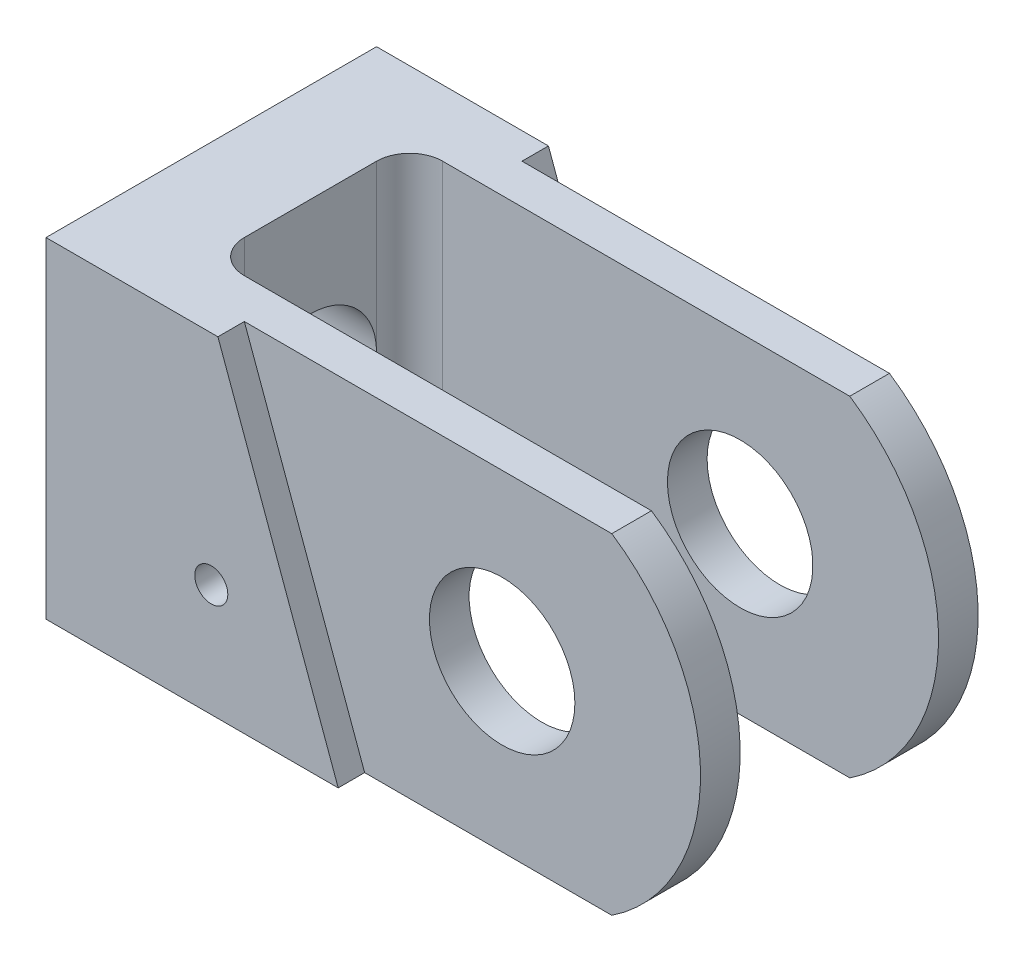
SolidWorks part; units mm, degrees
ref_plane "Front Plane" through (0, 0, 0) normal (0, 0, 1) x (1, 0, 0)
ref_plane "Top Plane" through (0, 0, 0) normal (0, 1, 0) x (1, 0, 0)
ref_plane "Right Plane" through (0, 0, 0) normal (1, 0, 0) x (0, 0, -1)
sketch "Sketch1" plane through (0, 0, 0) normal (0, 0, 1) x (1, 0, 0)
  line L1 (35.4458, -24.1953) -> (-46.1373, -24.1953)
  line L3 (35.4458, 25.8047) -> (-46.1373, 25.8047)
  line L4 (-46.1373, -24.1953) -> (-46.1373, 25.8047)
  line L5 (38.9579, -21.4704) -> (-46.1373, 25.8047) construction
  line L6 (38.9579, 23.0799) -> (-46.1373, -24.1953) construction
  circle A0 centre (18.8627, 0.8047) radius 11
  arc A2 (35.4458, -24.1953) -> (35.4458, 25.8047) centre (18.8627, 0.8047) ccw
  point P0 (-1.1373, 0.8047)
  dimension "D3" = 22
  dimension "D1" = 50
  dimension "D4" = 65
extrude "Boss-Extrude1" add sketch "Sketch1" along normal blind 50
sketch "Sketch2" plane through (-46.1373, 0, 0) normal (-1, 0, 0) x (0, 0, 1)
  line L0 (50, 25.8047) -> (0, 25.8047) construction
  line L1 (50, 25.8047) -> (50, -24.1953) construction
  circle A0 centre (25, 0.8047) radius 17.5
  dimension "D1" = 35
  dimension "D2" = 25
  dimension "D3" = 25
extrude "Cut-Extrude1" cut sketch "Sketch2" against normal blind 2
sketch "Sketch3" plane through (-44.1373, 0, 0) normal (-1, 0, 0) x (0, 0, 1)
  line L0 (50, 25.8047) -> (0, 25.8047) construction
  line L1 (50, 25.8047) -> (50, -24.1953) construction
  circle A0 centre (25, 0.8047) radius 10
  dimension "D1" = 20
  dimension "D2" = 25
  dimension "D3" = 25
extrude "Cut-Extrude2" cut sketch "Sketch3" against normal through all
sketch "Sketch4" plane through (0, 0, 50) normal (0, 0, 1) x (1, 0, 0)
  line L0 (-20.1373, 25.8047) -> (-1.9388, -24.1953)
  line L1 (35.4458, 25.8047) -> (-46.1373, 25.8047) construction
  line L2 (-46.1373, -24.1953) -> (35.4458, -24.1953) construction
  line M3 (-46.1373, -24.1953) -> (35.4458, -24.1953)
  arc M4 (35.4458, -24.1953) -> (35.4458, 25.8047) centre (18.8627, 0.8047) ccw
  line M5 (35.4458, 25.8047) -> (-46.1373, 25.8047)
  circle M6 centre (18.8627, 0.8047) radius 11
  dimension "D1" = 26
  dimension "D2" = 110
extrude "Cut-Extrude3" cut sketch "Sketch4" against normal blind 4 and the other way through all contours L0 M5 M3 M4 M6 region at (7.6542, 24.9526, 50)
sketch "Sketch5" plane through (0, 0, 0) normal (0, 0, -1) x (-1, 0, 0)
  line L0 (20.1373, 25.8047) -> (1.9388, -24.1953)
  line L1 (-35.4458, 25.8047) -> (46.1373, 25.8047) construction
  line L2 (46.1373, -24.1953) -> (-35.4458, -24.1953) construction
  line M3 (46.1373, 25.8047) -> (-35.4458, 25.8047)
  arc M4 (-35.4458, 25.8047) -> (-35.4458, -24.1953) centre (-18.8627, 0.8047) ccw
  line M5 (-35.4458, -24.1953) -> (46.1373, -24.1953)
  circle M6 centre (-18.8627, 0.8047) radius 11
  dimension "D1" = 26
  dimension "D2" = 110
extrude "Cut-Extrude4" cut sketch "Sketch5" against normal blind 4 and the other way through all contours L0 M3 M4 M5 M6 region at (-10.2374, 1.0962, 0)
sketch "Sketch6" plane through (0, 25.8047, 0) normal (0, 1, 0) x (1, 0, 0)
  line L0 (-46.1373, -50) -> (-46.1373, 0) construction
  line L1 (-31.1373, -10) -> (58.8627, -10)
  line L2 (-31.1373, -10) -> (-31.1373, -40)
  line L3 (-31.1373, -40) -> (58.8627, -40)
  line L4 (58.8627, -10) -> (58.8627, -40)
  line L5 (-31.1373, -10) -> (58.8627, -40) construction
  line L6 (-31.1373, -40) -> (58.8627, -10) construction
  line L7 (-20.1373, 0) -> (-46.1373, 0) construction
  dimension "D1" = 90
  dimension "D2" = 30
  dimension "D3" = 15
  dimension "D4" = 10
extrude "Cut-Extrude5" cut sketch "Sketch6" against normal through all
sketch "Sketch7" plane through (0, 0, 50) normal (0, 0, 1) x (1, 0, 0)
  line L0 (-46.1373, 25.8047) -> (-46.1373, -24.1953) construction
  line L1 (-46.1373, -24.1953) -> (-1.9388, -24.1953) construction
  circle A0 centre (-21.1373, -7.1953) radius 2.5
  dimension "D3" = 5
  dimension "D1" = 25
  dimension "D2" = 17
extrude "Cut-Extrude6" cut sketch "Sketch7" against normal through all
fillet "Fillet2" radius 5 2 edges at (-31.1373, 0.8047, 40) (-31.1373, 0.8047, 10)
